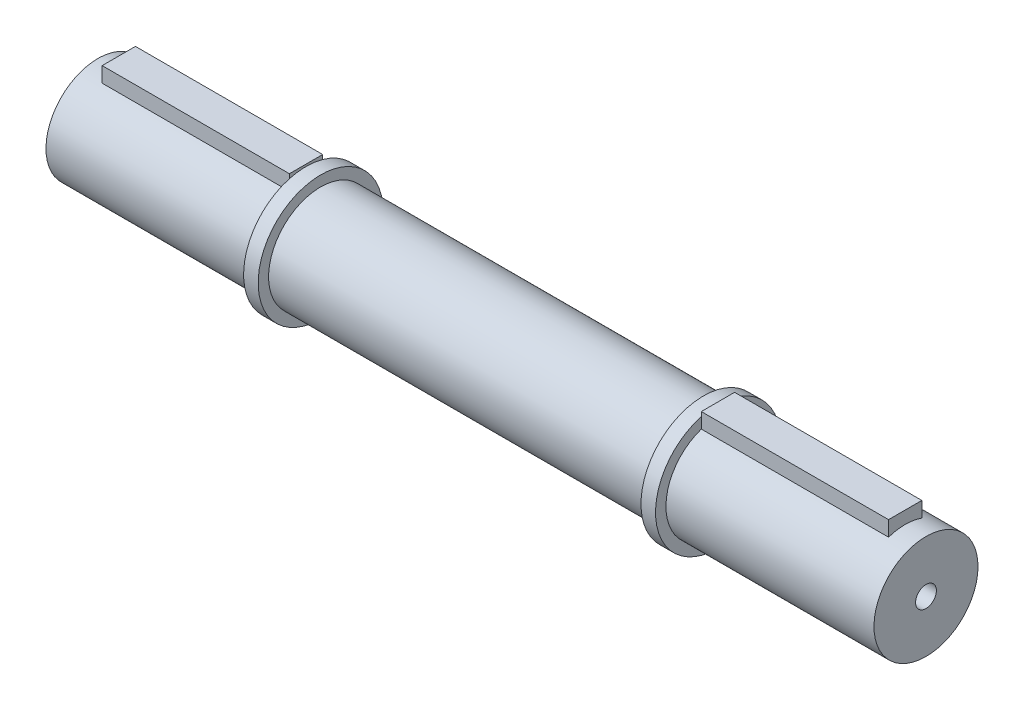
SolidWorks part; units mm, degrees
material "Acero al carbono no aleado"
ref_plane "Alzado" through (0, 0, 0) normal (0, 0, 1) x (1, 0, 0)
ref_plane "Planta" through (0, 0, 0) normal (0, 1, 0) x (1, 0, 0)
ref_plane "Vista lateral" through (0, 0, 0) normal (1, 0, 0) x (0, 0, -1)
sketch "Croquis1" plane through (0, 0, 0) normal (1, 0, 0) x (0, 0, -1)
  circle A0 centre (0, 0) radius 12.5
  dimension "D1" = 25
extrude "Saliente-Extruir1" add sketch "Croquis1" along normal mid plane 199
ref_plane "Plano1" through (46, 0, 0) normal (1, 0, 0) x (0, 0, -1)
ref_plane "Plano2" through (49.5, 0, 0) normal (-1, 0, 0) x (0, 0, 1)
sketch "Croquis2" plane through (46, 0, 0) normal (1, 0, 0) x (0, 0, -1)
  circle A0 centre (0, 0) radius 15
  dimension "D1" = 30
extrude "Saliente-Extruir2" add sketch "Croquis2" along normal up to surface (3.5 mm away) up to plane "Plano2"
sketch "Croquis4" plane through (49.5, 0, 0) normal (-1, 0, 0) x (0, 0, 1)
  line L0 (0, 0) -> (0, 15.5) construction
  line L1 (4, 15.5) -> (-4, 15.5)
  line L2 (-4, 15.5) -> (-4, 11.8427)
  line L3 (-4, 11.8427) -> (4, 11.8427)
  line L4 (4, 15.5) -> (4, 11.8427)
  line L5 (0, 0) -> (0, -12.5) construction
  circle A0 centre (0, 0) radius 12.5 construction
  circle A1 centre (0, 0) radius 12.5 construction
  point P9 (0, 11.8427)
  dimension "D1" = 28
  dimension "D2" = 8
extrude "Saliente-Extruir3" add sketch "Croquis4" against normal offset from surface (45 mm away) 5 up to face at (99.5, 0, -12.5)
ref_plane "Plano3" through (-49.5, 0, 0) normal (-1, 0, 0) x (0, 0, 1)
extrude "Saliente-Extruir4" add sketch "Croquis4<2>" along normal offset from surface (45 mm away) 5 from surface up to face at (-99.5, 0, -12.5) starting at plane "Plano3"
sketch "Croquis4<2>" plane through (49.5, 0, 0) normal (-1, 0, 0) x (0, 0, 1) same geometry as "Croquis4"
ref_plane "Plano4" through (-46, 0, 0) normal (1, 0, 0) x (0, 0, -1)
extrude "Saliente-Extruir5" add sketch "Croquis2<2>" against normal up to surface (95.5 mm away) from surface up to plane "Plano3" starting at plane "Plano4"
sketch "Croquis2<2>" plane through (46, 0, 0) normal (1, 0, 0) x (0, 0, -1) same geometry as "Croquis2"
hole_wizard "Taladro roscado M61" positions "Croquis5" profile "Croquis6" tap size "M6" standard "ISO" end condition through all
sketch "Croquis5" plane through (99.5, 0, 0) normal (1, 0, 0) x (0, 0, -1)
  point P0 (0, 0)
sketch "Croquis6" plane through (99.5, 0, 0) normal (0, 1, 0) x (0, 0, -1)
  line L0 (0, 0) -> (0, 199)
  line L1 (0, 199) -> (2.5, 199)
  line L2 (2.5, 199) -> (2.5, 0)
  line L5 (2.5, 0) -> (0, 0)
  line L11 (0, -6.35) -> (0, 107.95) construction
  dimension "Diámetro de perforador para roscar hasta el siguiente" = 5
  dimension "Profundidad de perforador para roscar hasta el siguiente" = 199
cosmetic thread "Rosca de taladro1" parameters "D2"=6
sketch "Croquis7" plane through (0, 0, 0) normal (0, 0, 1) x (1, 0, 0)
  line L0 (-1000, 0) -> (49000, 0) construction
